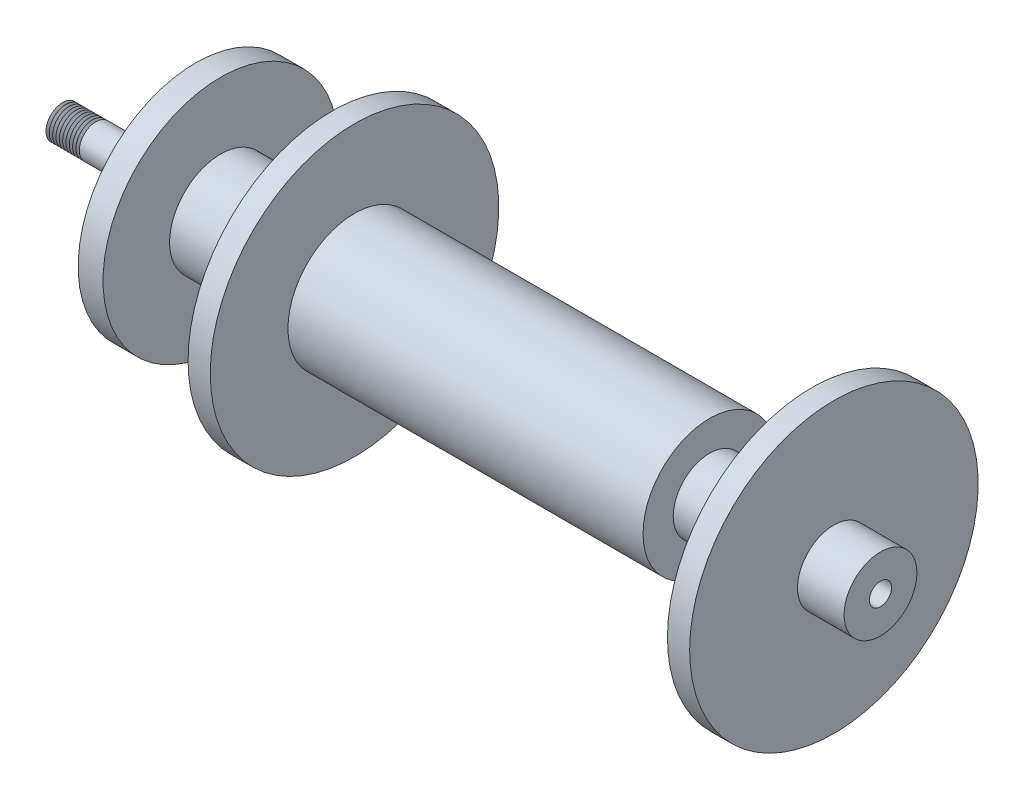
SolidWorks part; units mm, degrees
ref_plane "Ön Düzlem" through (0, 0, 0) normal (0, 0, 1) x (1, 0, 0)
ref_plane "Üst Düzlem" through (0, 0, 0) normal (0, 1, 0) x (1, 0, 0)
ref_plane "Sağ Düzlem" through (0, 0, 0) normal (1, 0, 0) x (0, 0, -1)
sketch "Çizim1" plane through (0, 0, 0) normal (0, 0, 1) x (1, 0, 0)
  line L0 (-200.7779, 0) -> (60, 0) construction
  line L1 (0, 173.0917) -> (0, -176.8793) construction
  line L2 (-90, 65) -> (-80, 65)
  line L3 (-90, 20) -> (-90, 65)
  line L4 (-80, 65) -> (-80, 30)
  line L5 (-80, 30) -> (80, 30)
  line L6 (104.1644, 30) -> (101.7671, 16.4047)
  line L7 (60, 20) -> (-75, 20)
  line L8 (-75, 20) -> (-75, 21.5)
  line L9 (-75, 21.5) -> (-85, 21.5)
  line L10 (-85, 21.5) -> (-85, 20)
  line L11 (-85, 20) -> (-90, 20)
  line L12 (60, 20) -> (60, 2.5)
  line L13 (126, 30) -> (126, 65)
  line L14 (126, 65) -> (136, 65)
  line L15 (80, 30) -> (80, 16.4047)
  line L16 (80, 16.4047) -> (156.9823, 16.4047)
  line L17 (156.9823, 16.4047) -> (156.9823, 5)
  line L18 (136, 65) -> (136, 16.4047)
  line L20 (104.1644, 30) -> (126, 30)
  line L21 (60, 2.5) -> (146.9823, 2.5)
  line L22 (146.9823, 2.5) -> (146.9823, 5)
  line L23 (146.9823, 5) -> (156.9823, 5)
  line L24 (60, 0) -> (201.4318, 0) construction
  dimension "D1" = 20
  dimension "D2" = 1.5
  dimension "D3" = 10
  dimension "D4" = 35
  dimension "D5" = 10
  dimension "D6" = 10
  dimension "D7" = 5
  dimension "D8" = 150
  dimension "D9" = 246.9823
  dimension "D10" = 20
  dimension "D11" = 10
  dimension "D12" = 80
  dimension "D13" = 46
  dimension "D14" = 10
revolve "Döndür1" add sketch "Çizim1" angle 360 about L0 region at (32.2075, 21.2148, 0) region at (103.5511, 23.0991, 0)
sketch "Çizim6" plane through (-80, 0, 0) normal (1, 0, 0) x (0, 0, -1)
  circle A0 centre (0, 0) radius 50
  dimension "D1" = 100
curve "Helis/Spiral1" pitch 17.2727 height 190 turns 11
sketch "Çizim7" [suppressed] plane through (0, 0, 0) normal (0, 1, 0) x (1, 0, 0)
  line L0 (-80, -60) -> (-80, 60) construction
  circle A0 centre (-80, -50) radius 4
  spline S0 degree 3 poles (-80, -50) (-79.8167, -50) (-79.4491, -49.3289) (-78.8986, -46.349) (-78.3478, -41.5153) (-77.7971, -35.0209) (-77.2464, -27.1258) (-76.6957, -18.1456) (-76.1449, -8.4396) (-75.5942, 1.604) (-75.0435, 11.5834) (-74.4928, 21.0995) (-73.942, 29.7716) (-73.3913, 37.2529) (-72.8406, 43.2441) (-72.2899, 47.5055) (-71.7391, 49.8667) (-71.1884, 50.2333) (-70.6377, 48.5906) (-70.087, 45.0043) (-69.5362, 39.6179) (-68.9855, 32.6467) (-68.4348, 24.3698) (-67.8841, 15.118) (-67.3333, 5.2615) (-66.7826, -4.8054) (-66.2319, -14.6802) (-65.6812, -23.9677) (-65.1304, -32.2965) (-64.5797, -39.3335) (-64.029, -44.7972) (-63.4783, -48.469) (-62.9275, -50.2021) (-62.3768, -49.9271) (-61.8261, -47.655) (-61.2754, -43.4768) (-60.7246, -37.5596) (-60.1739, -30.14) (-59.6232, -21.5148) (-59.0725, -12.029) (-58.5217, -2.062) (-57.971, 7.9874) (-57.4203, 17.7173) (-56.8696, 26.7385) (-56.3188, 34.6903) (-55.7681, 41.2544) (-55.2174, 46.1683) (-54.6667, 49.2356) (-54.1159, 50.3335) (-53.5652, 49.418) (-53.0145, 46.5259) (-52.4638, 41.7727) (-51.913, 35.3487) (-51.3623, 27.5107) (-50.8116, 18.5724) (-50.2609, 8.8911) (-49.7101, -1.1458) (-49.1594, -11.1369) (-48.6087, -20.6825) (-48.058, -29.4008) (-47.5072, -36.9431) (-46.9565, -43.0077) (-46.4058, -47.352) (-45.8551, -49.8023) (-45.3043, -50.2605) (-44.7536, -48.7083) (-44.2029, -45.2078) (-43.6522, -39.899) (-43.1014, -32.9943) (-42.5507, -24.7698) (-42, -15.5545) (-41.4493, -5.7171) (-40.8986, 4.349) (-40.3478, 14.2411) (-39.7971, 23.5636) (-39.2464, 31.9436) (-38.6957, 39.0459) (-38.1449, 44.5863) (-37.5942, 48.3433) (-37.0435, 50.1666) (-36.4928, 49.9833) (-35.942, 47.8007) (-35.3913, 43.706) (-34.8406, 37.8632) (-34.2899, 30.5058) (-33.7391, 21.9282) (-33.1884, 12.4735) (-32.6377, 2.5199) (-32.087, -7.5345) (-31.5362, -17.2875) (-30.9855, -26.3491) (-30.4348, -34.3567) (-29.8841, -40.9901) (-29.3333, -45.9838) (-28.7826, -49.1383) (-28.2319, -50.3272) (-27.6812, -49.5031) (-27.1304, -46.6989) (-26.5797, -42.0267) (-26.029, -35.6736) (-25.4783, -27.8934) (-24.9275, -18.9976) (-24.3768, -9.3419) (-23.8261, 0.6875) (-23.2754, 10.6894) (-22.7246, 20.2637) (-22.1739, 29.0275) (-21.6232, 36.6302) (-21.0725, 42.7677) (-20.5217, 47.1946) (-19.971, 49.7336) (-19.4203, 50.2834) (-18.8696, 48.8218) (-18.3188, 45.4074) (-17.7681, 40.1768) (-17.2174, 33.339) (-16.6667, 25.1678) (-16.1159, 15.9898) (-15.5652, 6.1723) (-15.0145, -3.8922) (-14.4638, -13.8009) (-13.913, -23.1576) (-13.3623, -31.5881) (-12.8116, -38.755) (-12.2609, -44.3717) (-11.7101, -48.2136) (-11.1594, -50.127) (-10.6087, -50.0353) (-10.058, -47.9423) (-9.5072, -43.9316) (-8.9565, -38.1636) (-8.4058, -30.8691) (-7.8551, -22.3399) (-7.3043, -12.9171) (-6.7536, -2.9776) (-6.2029, 7.081) (-5.6522, 16.8564) (-5.1014, 25.9575) (-4.5507, 34.0203) (-4, 40.7223) (-3.4493, 45.7955) (-2.8986, 49.0369) (-2.3478, 50.3168) (-1.7971, 49.5841) (-1.2464, 46.868) (-0.6957, 42.2773) (-0.1449, 35.9954) (0.4058, 28.2738) (0.9565, 19.4213) (1.5072, 9.7919) (2.058, -0.2292) (2.6087, -10.2411) (3.1594, -19.8433) (3.7101, -28.6519) (4.2609, -36.3143) (4.8116, -42.5243) (5.3623, -47.0332) (5.913, -49.6609) (6.4638, -50.3022) (7.0145, -48.9314) (7.5652, -45.6034) (8.1159, -40.4512) (8.6667, -33.6811) (9.2174, -25.5637) (9.7681, -16.4238) (10.3188, -6.6269) (10.8696, 3.435) (11.4203, 13.3596) (11.971, 22.7497) (12.5217, 31.2299) (13.0725, 38.4609) (13.6232, 44.1535) (14.1739, 48.08) (14.7246, 50.0833) (15.2754, 50.0833) (15.8261, 48.08) (16.3768, 44.1535) (16.9275, 38.4609) (17.4783, 31.2299) (18.029, 22.7497) (18.5797, 13.3596) (19.1304, 3.435) (19.6812, -6.6269) (20.2319, -16.4238) (20.7826, -25.5637) (21.3333, -33.6811) (21.8841, -40.4512) (22.4348, -45.6034) (22.9855, -48.9314) (23.5362, -50.3022) (24.087, -49.6609) (24.6377, -47.0332) (25.1884, -42.5243) (25.7391, -36.3143) (26.2899, -28.6519) (26.8406, -19.8433) (27.3913, -10.2411) (27.942, -0.2292) (28.4928, 9.7919) (29.0435, 19.4213) (29.5942, 28.2738) (30.1449, 35.9954) (30.6957, 42.2773) (31.2464, 46.868) (31.7971, 49.5841) (32.3478, 50.3168) (32.8986, 49.0369) (33.4493, 45.7955) (34, 40.7223) (34.5507, 34.0203) (35.1014, 25.9575) (35.6522, 16.8564) (36.2029, 7.081) (36.7536, -2.9776) (37.3043, -12.9171) (37.8551, -22.3399) (38.4058, -30.8691) (38.9565, -38.1636) (39.5072, -43.9316) (40.058, -47.9423) (40.6087, -50.0353) (41.1594, -50.127) (41.7101, -48.2136) (42.2609, -44.3717) (42.8116, -38.755) (43.3623, -31.5881) (43.913, -23.1576) (44.4638, -13.8009) (45.0145, -3.8922) (45.5652, 6.1723) (46.1159, 15.9898) (46.6667, 25.1678) (47.2174, 33.339) (47.7681, 40.1768) (48.3188, 45.4074) (48.8696, 48.8218) (49.4203, 50.2834) (49.971, 49.7336) (50.5217, 47.1946) (51.0725, 42.7677) (51.6232, 36.6302) (52.1739, 29.0275) (52.7246, 20.2637) (53.2754, 10.6894) (53.8261, 0.6875) (54.3768, -9.3419) (54.9275, -18.9976) (55.4783, -27.8934) (56.029, -35.6736) (56.5797, -42.0267) (57.1304, -46.6989) (57.6812, -49.5031) (58.2319, -50.3272) (58.7826, -49.1383) (59.3333, -45.9838) (59.8841, -40.9901) (60.4348, -34.3567) (60.9855, -26.3491) (61.5362, -17.2875) (62.087, -7.5345) (62.6377, 2.5199) (63.1884, 12.4735) (63.7391, 21.9282) (64.2899, 30.5058) (64.8406, 37.8632) (65.3913, 43.706) (65.942, 47.8007) (66.4928, 49.9833) (67.0435, 50.1666) (67.5942, 48.3433) (68.1449, 44.5863) (68.6957, 39.0459) (69.2464, 31.9436) (69.7971, 23.5636) (70.3478, 14.2411) (70.8986, 4.349) (71.4493, -5.7171) (72, -15.5545) (72.5507, -24.7698) (73.1014, -32.9943) (73.6522, -39.899) (74.2029, -45.2078) (74.7536, -48.7083) (75.3043, -50.2605) (75.8551, -49.8023) (76.4058, -47.352) (76.9565, -43.0077) (77.5072, -36.9431) (78.058, -29.4008) (78.6087, -20.6825) (79.1594, -11.1369) (79.7101, -1.1458) (80.2609, 8.8911) (80.8116, 18.5724) (81.3623, 27.5107) (81.913, 35.3487) (82.4638, 41.7727) (83.0145, 46.5259) (83.5652, 49.418) (84.1159, 50.3335) (84.6667, 49.2356) (85.2174, 46.1683) (85.7681, 41.2544) (86.3188, 34.6903) (86.8696, 26.7385) (87.4203, 17.7173) (87.971, 7.9874) (88.5217, -2.062) (89.0725, -12.029) (89.6232, -21.5148) (90.1739, -30.14) (90.7246, -37.5596) (91.2754, -43.4768) (91.8261, -47.655) (92.3768, -49.9271) (92.9275, -50.2021) (93.4783, -48.469) (94.029, -44.7972) (94.5797, -39.3335) (95.1304, -32.2965) (95.6812, -23.9677) (96.2319, -14.6802) (96.7826, -4.8054) (97.3333, 5.2615) (97.8841, 15.118) (98.4348, 24.3698) (98.9855, 32.6467) (99.5362, 39.6179) (100.087, 45.0043) (100.6377, 48.5906) (101.1884, 50.2333) (101.7391, 49.8667) (102.2899, 47.5055) (102.8406, 43.2441) (103.3913, 37.2529) (103.942, 29.7716) (104.4928, 21.0995) (105.0435, 11.5834) (105.5942, 1.604) (106.1449, -8.4396) (106.6957, -18.1456) (107.2464, -27.1258) (107.7971, -35.0209) (108.3478, -41.5153) (108.8986, -46.349) (109.4491, -49.3289) (109.8167, -50) (110, -50) knots 0 0 0 0 0.002899 0.005797 0.008696 0.011594 0.014493 0.017391 0.02029 0.023188 0.026087 0.028986 0.031884 0.034783 0.037681 0.04058 0.043478 0.046377 0.049275 0.052174 0.055072 0.057971 0.06087 0.063768 0.066667 0.069565 0.072464 0.075362 0.078261 0.081159 0.084058 0.086957 0.089855 0.092754 0.095652 0.098551 0.101449 0.104348 0.107246 0.110145 0.113043 0.115942 0.118841 0.121739 0.124638 0.127536 0.130435 0.133333 0.136232 0.13913 0.142029 0.144928 0.147826 0.150725 0.153623 0.156522 0.15942 0.162319 0.165217 0.168116 0.171014 0.173913 0.176812 0.17971 0.182609 0.185507 0.188406 0.191304 0.194203 0.197101 0.2 0.202899 0.205797 0.208696 0.211594 0.214493 0.217391 0.22029 0.223188 0.226087 0.228986 0.231884 0.234783 0.237681 0.24058 0.243478 0.246377 0.249275 0.252174 0.255072 0.257971 0.26087 0.263768 0.266667 0.269565 0.272464 0.275362 0.278261 0.281159 0.284058 0.286957 0.289855 0.292754 0.295652 0.298551 0.301449 0.304348 0.307246 0.310145 0.313043 0.315942 0.318841 0.321739 0.324638 0.327536 0.330435 0.333333 0.336232 0.33913 0.342029 0.344928 0.347826 0.350725 0.353623 0.356522 0.35942 0.362319 0.365217 0.368116 0.371014 0.373913 0.376812 0.37971 0.382609 0.385507 0.388406 0.391304 0.394203 0.397101 0.4 0.402899 0.405797 0.408696 0.411594 0.414493 0.417391 0.42029 0.423188 0.426087 0.428986 0.431884 0.434783 0.437681 0.44058 0.443478 0.446377 0.449275 0.452174 0.455072 0.457971 0.46087 0.463768 0.466667 0.469565 0.472464 0.475362 0.478261 0.481159 0.484058 0.486957 0.489855 0.492754 0.495652 0.498551 0.501449 0.504348 0.507246 0.510145 0.513043 0.515942 0.518841 0.521739 0.524638 0.527536 0.530435 0.533333 0.536232 0.53913 0.542029 0.544928 0.547826 0.550725 0.553623 0.556522 0.55942 0.562319 0.565217 0.568116 0.571014 0.573913 0.576812 0.57971 0.582609 0.585507 0.588406 0.591304 0.594203 0.597101 0.6 0.602899 0.605797 0.608696 0.611594 0.614493 0.617391 0.62029 0.623188 0.626087 0.628986 0.631884 0.634783 0.637681 0.64058 0.643478 0.646377 0.649275 0.652174 0.655072 0.657971 0.66087 0.663768 0.666667 0.669565 0.672464 0.675362 0.678261 0.681159 0.684058 0.686957 0.689855 0.692754 0.695652 0.698551 0.701449 0.704348 0.707246 0.710145 0.713043 0.715942 0.718841 0.721739 0.724638 0.727536 0.730435 0.733333 0.736232 0.73913 0.742029 0.744928 0.747826 0.750725 0.753623 0.756522 0.75942 0.762319 0.765217 0.768116 0.771014 0.773913 0.776812 0.77971 0.782609 0.785507 0.788406 0.791304 0.794203 0.797101 0.8 0.802899 0.805797 0.808696 0.811594 0.814493 0.817391 0.82029 0.823188 0.826087 0.828986 0.831884 0.834783 0.837681 0.84058 0.843478 0.846377 0.849275 0.852174 0.855072 0.857971 0.86087 0.863768 0.866667 0.869565 0.872464 0.875362 0.878261 0.881159 0.884058 0.886957 0.889855 0.892754 0.895652 0.898551 0.901449 0.904348 0.907246 0.910145 0.913043 0.915942 0.918841 0.921739 0.924638 0.927536 0.930435 0.933333 0.936232 0.93913 0.942029 0.944928 0.947826 0.950725 0.953623 0.956522 0.95942 0.962319 0.965217 0.968116 0.971014 0.973913 0.976812 0.97971 0.982609 0.985507 0.988406 0.991304 0.994203 0.997101 1 1 1 1 construction
  dimension "D1" = 8
sketch "Çizim8" plane through (0, 0, 0) normal (0, 1, 0) x (1, 0, 0)
  circle A0 centre (-72.2282, -47.3713) radius 7.5
  dimension "D1" = 15
sweep "Süpür1" [suppressed] add profiles "Çizim8" path "Helis/Spiral1"
sketch "Çizim10" plane through (0, 0, 0) normal (0, 0, 1) x (1, 0, 0)
  line L0 (9.6682, 15) -> (9.6682, -15)
  line L1 (56.2517, 0) -> (-347.0383, 0) construction
  line L2 (9.6682, 15) -> (-115.3084, 15)
  line L3 (-115.3084, 23) -> (-115.3084, 15)
  line L4 (-115.3084, 15) -> (-115.3084, 7.5)
  line L5 (-151.5243, 7.5) -> (-115.3084, 7.5)
  line L6 (-199.5243, 7.5) -> (-201.0243, 7.5)
  line L7 (-151.5243, 55.0592) -> (-151.5243, 53)
  line L8 (-115.3084, 23) -> (-140.3084, 23)
  line L9 (-140.3084, 23) -> (-140.3084, 53)
  line L10 (-140.3084, 53) -> (-151.5243, 53)
  line L11 (-151.5243, 53) -> (-151.5243, 7.5)
  line L12 (-142.7613, 0) -> (9.6682, 0)
  line L13 (-211.5243, 7.5) -> (-210.7743, 6.201)
  line L14 (-151.5243, 7.5) -> (-196.5243, 7.5)
  line L15 (-211.5243, 7.5) -> (-211.5243, 0)
  line L16 (-211.5243, 0) -> (-142.7613, 0)
  line L17 (-210.7743, 6.201) -> (-210.0243, 7.5)
  line L18 (-209.2743, 6.201) -> (-208.5243, 7.5)
  line L19 (-210.0243, 7.5) -> (-209.2743, 6.201)
  line L20 (-207.7743, 6.201) -> (-207.0243, 7.5)
  line L21 (-208.5243, 7.5) -> (-207.7743, 6.201)
  line L22 (-206.2743, 6.201) -> (-205.5243, 7.5)
  line L23 (-207.0243, 7.5) -> (-206.2743, 6.201)
  line L24 (-204.7743, 6.201) -> (-204.0243, 7.5)
  line L25 (-205.5243, 7.5) -> (-204.7743, 6.201)
  line L26 (-203.2743, 6.201) -> (-202.5243, 7.5)
  line L27 (-204.0243, 7.5) -> (-203.2743, 6.201)
  line L28 (-201.7743, 6.201) -> (-201.0243, 7.5)
  line L29 (-202.5243, 7.5) -> (-201.7743, 6.201)
  line L30 (-200.2743, 6.201) -> (-199.5243, 7.5)
  line L31 (-201.0243, 7.5) -> (-200.2743, 6.201)
  line L32 (-198.7743, 6.201) -> (-198.0243, 7.5)
  line L33 (-199.5243, 7.5) -> (-198.7743, 6.201)
  line L34 (-197.2743, 6.201) -> (-196.5243, 7.5)
  line L35 (-198.0243, 7.5) -> (-197.2743, 6.201)
  line L36 (-151.5243, 23) -> (-191.5243, 23)
  line L37 (-151.5243, 90) -> (-388.2261, 90) construction
  line L38 (-151.5243, 55.0592) -> (-163.2567, 55.0592)
  line L39 (-262.4252, 110) -> (-380.1337, 110)
  line L40 (-380.1337, 110) -> (-380.1337, 90)
  line L41 (-380.1337, 90) -> (-293.9746, 90)
  line L42 (-191.5243, 23) -> (-200.2316, 47.0464)
  spline S0 degree 3 poles (-163.2567, 55.0592) (-179.3764, 74.2393) (-164.9882, 98.1077) (-247.0242, 110.3206) (-258.8893, 110) (-262.4252, 110) knots 0 0 0 0 0.857299 0.957299 1 1 1 1
  spline S1 degree 2 poles (-200.2316, 47.0464) (-217.4958, 94.7237) (-293.9746, 90) knots 0 0 0 1 1 1
  dimension "D1" = 30
  dimension "D2" = 8
  dimension "D3" = 25
  dimension "D4" = 7.5
  dimension "D5" = 60
  dimension "D6" = 1.5
  dimension "D7" = 60
  dimension "D8" = 60
  dimension "D10" = 20
  dimension "D11" = 30
  dimension "D12" = 90
  dimension "D14" = 40
  dimension "D9" = 10
revolve "Döndür2" add sketch "Çizim10" angle 360 about L1 region at (-83.106, 6.4554, 0) region at (-115.8899, 11.25, 0)
sketch "Çizim14" plane through (0, 0, 0) normal (0, 0, 1) x (1, 0, 0)
  line L0 (-85.0836, 21) -> (-75, 21)
  line L2 (-75, 21.5) -> (-75, -21.5) construction
  line L3 (-73.0836, 18) -> (-85.0836, 18)
  line L5 (-85, 15) -> (-71.0973, 15)
  line L6 (-85, -20) -> (-85, 20) construction
  line L7 (-85.0836, 18) -> (-85.0836, 21)
  line L8 (-73.0836, 18) -> (-73.0836, 21)
  line L9 (-73.0836, 21) -> (-75, 21)
  line L10 (-85.0836, 21) -> (-85.0836, 21.6104)
  line L11 (-85.0836, 21.6104) -> (-74.5277, 21.6104)
  line L12 (-74.5277, 21.6104) -> (-74.5277, 21)
  circle A0 centre (-82.0836, 18) radius 3
  circle A1 centre (-76.0836, 18) radius 3
  dimension "D1" = 6
revolve "Döndür3" add sketch "Çizim14" angle 360 about axis through (56.2517, 0, 0) along (1, 0, 0) region at (-79.8056, 21.3052, 0)
revolve "Kes-Döndür1" cut sketch "Çizim14<3>" angle 360 about axis through (56.2517, 0, 0) along (1, 0, 0) region at (-84.4134, 20.3299, 0) region at (-79.0836, 20.3299, 0) region at (-82.0836, 19.2732, 0) region at (-73.7537, 20.3299, 0) region at (-76.0836, 19.2732, 0)
sketch "Çizim14<3>" plane through (0, 0, 0) normal (0, 0, 1) x (1, 0, 0) same geometry as "Çizim14"
revolve "Döndür4" add sketch "Çizim14<4>" angle 360 about axis through (56.2517, 0, 0) along (1, 0, 0) region at (-82.0836, 19.2732, 0) region at (-82.0836, 16.7267, 0) region at (-76.0836, 19.2732, 0) region at (-76.0836, 16.7267, 0)
sketch "Çizim14<4>" plane through (0, 0, 0) normal (0, 0, 1) x (1, 0, 0) same geometry as "Çizim14"
